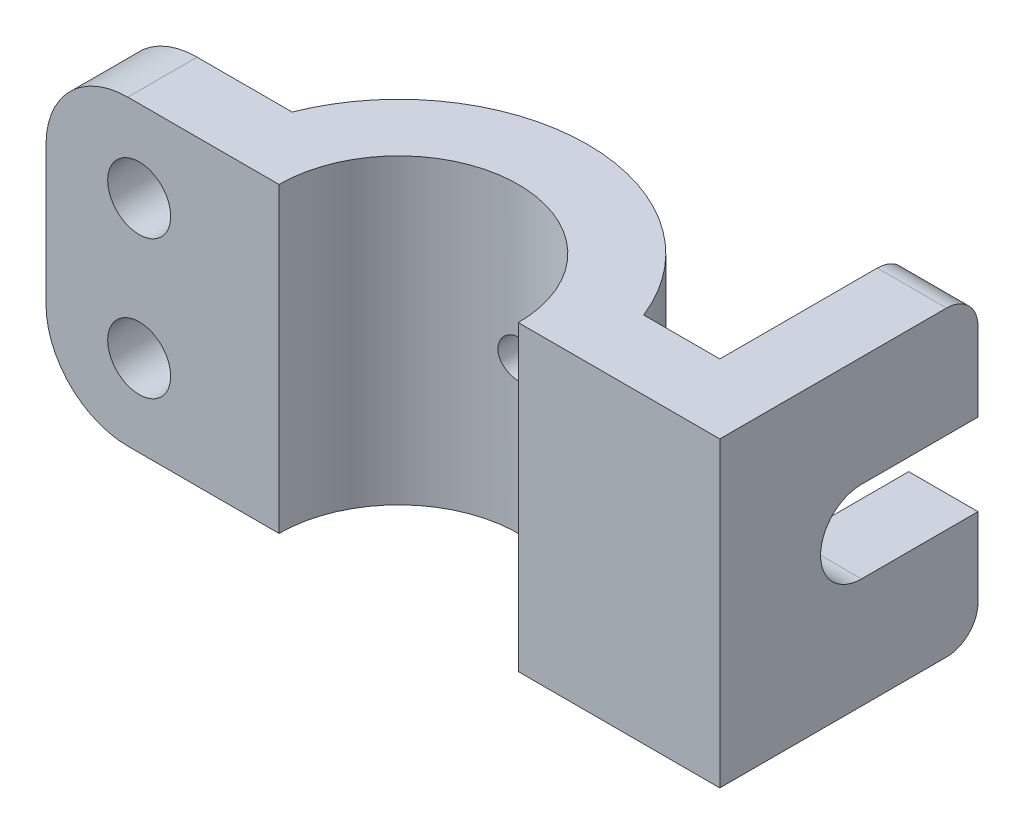
SolidWorks part; units mm, degrees
ref_plane "Plano frontal" through (0, 0, 0) normal (0, 0, 1) x (1, 0, 0)
ref_plane "Plano superior" through (0, 0, 0) normal (0, 1, 0) x (1, 0, 0)
ref_plane "Plano direito" through (0, 0, 0) normal (1, 0, 0) x (0, 0, -1)
sketch "Esboço1" plane through (0, 0, 0) normal (0, 1, 0) x (1, 0, 0)
  line L0 (0, 0) -> (0, 11)
  line L1 (0, 11) -> (96, 11)
  line L2 (96, 11) -> (96, 41)
  line L3 (96, 41) -> (107, 41)
  line L4 (107, 0) -> (0, 0)
  line L5 (107, 41) -> (107, 0)
  circle A0 centre (56, 0) radius 19
  circle A1 centre (56, 0) radius 30
  dimension "D5" = 38
  dimension "D6" = 60
  dimension "D7" = 51
  dimension "D1" = 11
  dimension "D2" = 107
  dimension "D3" = 96
  dimension "D4" = 41
extrude "Ressalto-extrusão1" add sketch "Esboço1" along normal blind 48 contours L1 A1 L4 A0 | A1 L1 L0 L4 | L1 A1 A0 | L4 A1 L1 A0 | A1 L4 L5 L3 L2 L1 region at (13.3504, 0, -5.5712) region at (32.434, 0, -5.6089) region at (56, 0, -20.193) region at (99.2544, 0, -17.4354) region at (79.566, 0, -5.6089)
sketch "Esboço2" plane through (0, 0, -11) normal (0, 0, -1) x (-1, 0, 0)
  line L0 (0, 48) -> (-28.0894, 48) construction
  line L1 (0, 0) -> (-28.0894, 0) construction
  circle A0 centre (-14.7954, 35) radius 5
  circle A1 centre (-14.7954, 13) radius 5
  dimension "D1" = 10
  dimension "D2" = 10
  dimension "D3" = 22
  dimension "D4" = 13
  dimension "D5" = 13
extrude "Corte-extrusão1" cut sketch "Esboço2" against normal through all
fillet "Filete1" radius 13 2 edges at (0, 0, -5.5) (0, 48, -5.5)
sketch "Esboço3" plane through (0, 0, -11) normal (0, 0, -1) x (-1, 0, 0)
  line L0 (-28.0894, 48) -> (-83.9106, 48) construction
  circle A0 centre (-56, 24) radius 3
  dimension "D1" = 6
  dimension "D2" = 24
extrude "Corte-extrusão2" cut sketch "Esboço3" along normal through all
sketch "Esboço4" plane through (0, 0, -41) normal (0, 0, -1) x (-1, 0, 0)
  line L0 (-107, 48) -> (-107, 0) construction
  line L1 (-107, 30.5) -> (-96, 30.5)
  line L2 (-107, 30.5) -> (-107, 17.5)
  line L3 (-107, 17.5) -> (-96, 17.5)
  line L4 (-96, 30.5) -> (-96, 17.5)
  line L5 (-96, 48) -> (-96, 0) construction
  line L6 (-96, 0) -> (-107, 0) construction
  dimension "D1" = 13
  dimension "D2" = 17.5
extrude "Corte-extrusão3" cut sketch "Esboço4" against normal blind 25
fillet "Filete4" 2 edges at (101.5, 30.5, -16) (101.5, 17.5, -16) type full round first side face at (101.5, 30.5, -28.5) second side face at (101.5, 17.5, -28.5) middle face at (101.5, 24, -16)
fillet "Filete5" radius 5 2 edges at (101.5, 0, -41) (101.5, 48, -41)
